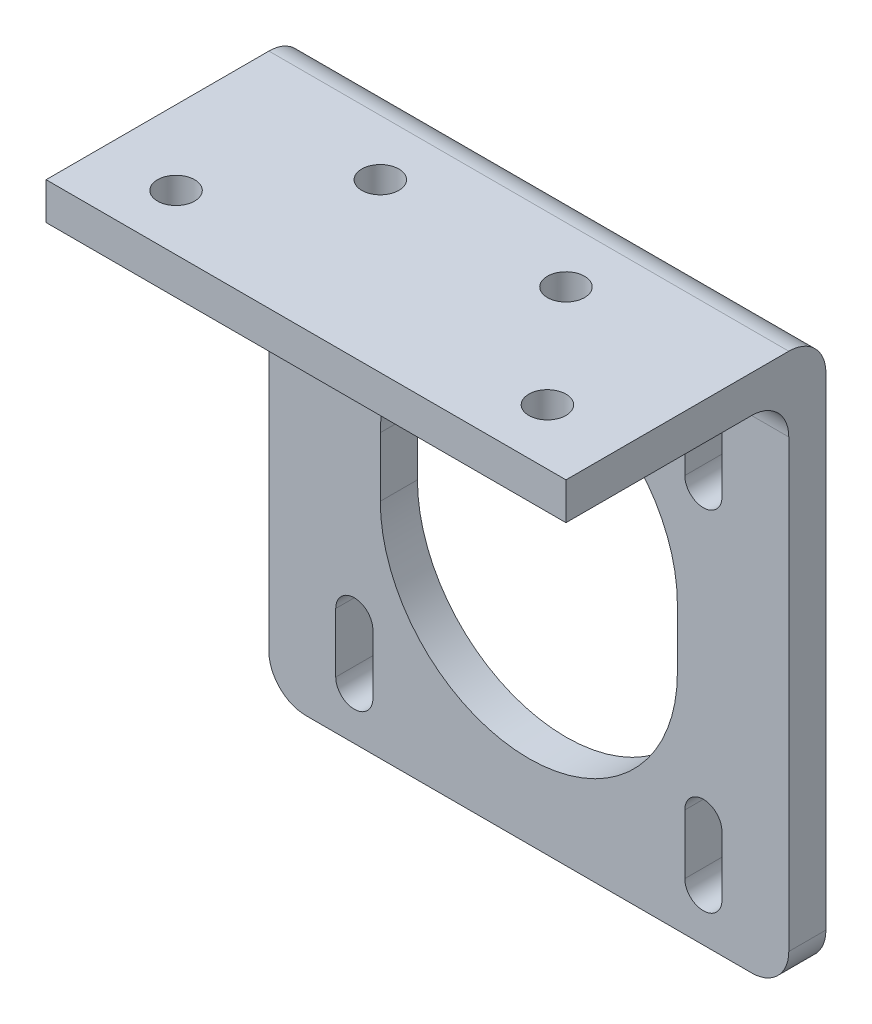
SolidWorks part; units mm, degrees
ref_plane "Front Plane" through (0, 0, 0) normal (0, 0, 1) x (1, 0, 0)
ref_plane "Top Plane" through (0, 0, 0) normal (0, 1, 0) x (1, 0, 0)
ref_plane "Right Plane" through (0, 0, 0) normal (1, 0, 0) x (0, 0, -1)
sketch "Sketch2" plane through (0, 0, 0) normal (0, 0, 1) x (1, 0, 0)
  line L1 (-30, -37.5) -> (30, -37.5)
  line L2 (-35, -32.5) -> (-35, 37.5)
  line L3 (-35, 37.5) -> (35, 37.5)
  line L4 (35, -32.5) -> (35, 37.5)
  line L5 (-35, -37.5) -> (35, 37.5) construction
  line L6 (-35, 37.5) -> (35, -37.5) construction
  arc A0 (30, -37.5) -> (35, -32.5) centre (30, -32.5) ccw
  arc A1 (-30, -37.5) -> (-35, -32.5) centre (-30, -32.5) cw
  point P0 (0, 0)
  dimension "D2" = 5
  dimension "D1" = 75
extrude "Boss-Extrude1" add sketch "Sketch2" along normal blind 5
sketch "Sketch3" plane through (0, 0, 5) normal (0, 0, 1) x (1, 0, 0)
  line L0 (-23.5, 24) -> (-23.5, 16) construction
  line L1 (-21, 24) -> (-21, 16)
  line L2 (-26, 24) -> (-26, 16)
  line L3 (-23.5, -23) -> (-23.5, -31) construction
  line L4 (-21, -23) -> (-21, -31)
  line L5 (-26, -23) -> (-26, -31)
  line L6 (23.5, 24) -> (23.5, 16) construction
  line L7 (26, 24) -> (26, 16)
  line L8 (21, 24) -> (21, 16)
  line L9 (23.5, -23) -> (23.5, -31) construction
  line L10 (26, -23) -> (26, -31)
  line L11 (21, -23) -> (21, -31)
  line L12 (-23.5, 20) -> (23.5, 20) construction
  line L13 (23.5, 20) -> (23.5, -27) construction
  line L14 (0, 0.5) -> (0, -7.5) construction
  line L15 (20, 0.5) -> (20, -7.5)
  line L16 (-20, 0.5) -> (-20, -7.5)
  arc A0 (-21, 24) -> (-26, 24) centre (-23.5, 24) ccw
  arc A1 (-26, 16) -> (-21, 16) centre (-23.5, 16) ccw
  arc A2 (-21, -23) -> (-26, -23) centre (-23.5, -23) ccw
  arc A3 (-26, -31) -> (-21, -31) centre (-23.5, -31) ccw
  arc A4 (26, 24) -> (21, 24) centre (23.5, 24) ccw
  arc A5 (21, 16) -> (26, 16) centre (23.5, 16) ccw
  arc A6 (26, -23) -> (21, -23) centre (23.5, -23) ccw
  arc A7 (21, -31) -> (26, -31) centre (23.5, -31) ccw
  arc A8 (20, 0.5) -> (-20, 0.5) centre (0, 0.5) ccw
  arc A9 (-20, -7.5) -> (20, -7.5) centre (0, -7.5) ccw
  point P2 (-23.5, 20)
  point P7 (-23.5, -27)
  point P14 (23.5, 20)
  point P21 (23.5, -27)
  point P28 (0, 20)
  point P32 (0, -3.5)
  point P40 (0, 0)
  point P41 (23.5, -3.5)
  dimension "D4" = 2.5
  dimension "D7" = 20
  dimension "D1" = 8
  dimension "D2" = 47
  dimension "D3" = 47
  dimension "D5" = 20
  dimension "D6" = 8
extrude "Cut-Extrude1" cut sketch "Sketch3" against normal through all
sketch "Sketch4" plane through (0, 0, 5) normal (0, 0, 1) x (1, 0, 0)
  line L0 (-35, 37.5) -> (-35, 32.5)
  line L1 (-35, 37.5) -> (-35, -32.5) construction
  line L2 (-35, 32.5) -> (35, 32.5)
  line L3 (35, -32.5) -> (35, 37.5) construction
  line L4 (35, 32.5) -> (35, 37.5)
  line L5 (35, 37.5) -> (-35, 37.5) construction
  line L6 (35, 37.5) -> (-35, 37.5)
  dimension "D1" = 5
extrude "Boss-Extrude2" add sketch "Sketch4" along normal blind 30
sketch "Sketch5" plane through (0, 32.5, 0) normal (0, -1, 0) x (1, 0, 0)
  line L0 (-12.5, 12.5) -> (12.5, 12.5) construction
  line L2 (-35, 5) -> (35, 5) construction
  line L3 (-25, 27.5) -> (25, 27.5) construction
  circle A0 centre (-12.5, 12.5) radius 2.5
  circle A1 centre (12.5, 12.5) radius 2.5
  circle A2 centre (-25, 27.5) radius 2.5
  circle A3 centre (25, 27.5) radius 2.5
  point P4 (0, 12.5)
  point P15 (0, 27.5)
  dimension "D1" = 5
  dimension "D2" = 25
  dimension "D3" = 7.5
  dimension "D4" = 15
  dimension "D5" = 50
extrude "Cut-Extrude2" cut sketch "Sketch5" against normal blind 30
fillet "Fillet1" radius 5 2 edges at (0, 32.5, 5) (0, 37.5, 0)
